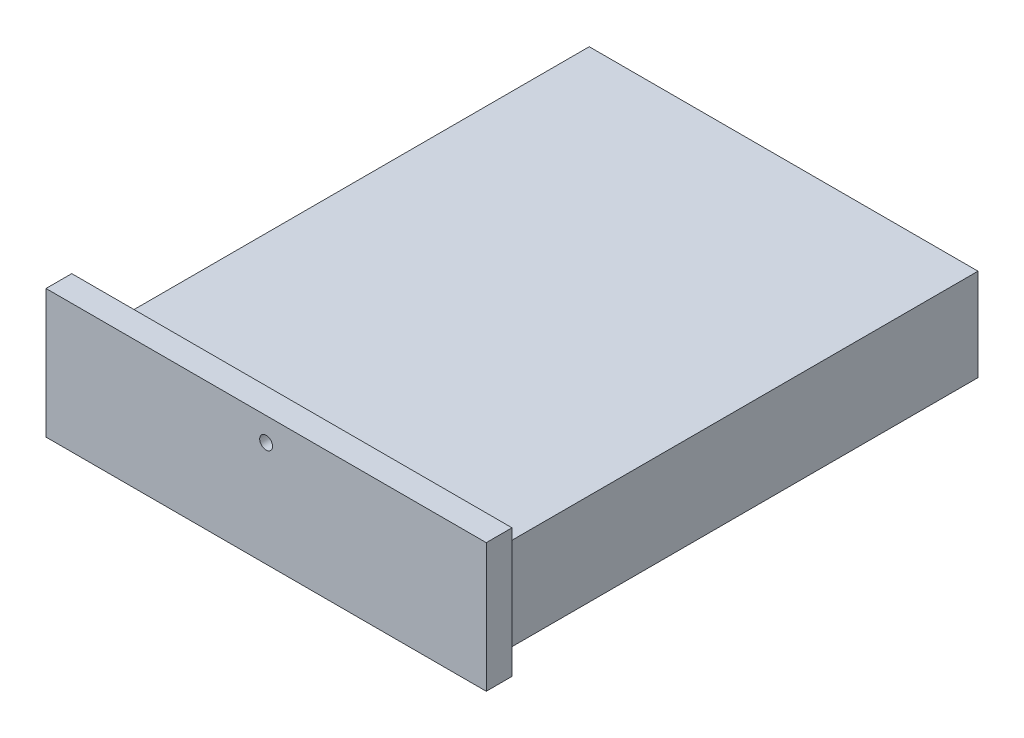
SolidWorks part; units mm, degrees
ref_plane "Front Plane" through (0, 0, 0) normal (0, 0, 1) x (1, 0, 0)
ref_plane "Top Plane" through (0, 0, 0) normal (0, 1, 0) x (1, 0, 0)
ref_plane "Right Plane" through (0, 0, 0) normal (1, 0, 0) x (0, 0, -1)
sketch "Sketch1" plane through (0, -22.3524, -0.0002) normal (0, 1, 0) x (1, 0, 0)
  line L4 (131.4337, 6.867) -> (131.3805, 6.867)
  line L5 (131.4337, 6.867) -> (131.3805, 6.867)
  line L6 (80.0805, 6.867) -> (80.0805, 25.967)
  line L7 (80.0805, 6.867) -> (80.0805, 25.967)
  line L14 (80.0805, 25.967) -> (64.9805, 25.967)
  line L15 (80.0805, 25.967) -> (64.9805, 25.967)
  line L16 (64.9805, 25.967) -> (64.9805, 5.967)
  line L17 (64.9805, 25.967) -> (64.9805, 5.967)
  line L26 (148.4829, 25.967) -> (133.3805, 25.967)
  line L27 (148.4829, 25.967) -> (133.3805, 25.967)
  line L28 (133.3805, 25.967) -> (133.3805, 5.967)
  line L29 (133.3805, 25.967) -> (133.3805, 5.967)
  line L75 (116.2805, 6.867) -> (114.2805, 6.867)
  line L76 (116.2805, 6.867) -> (114.2805, 6.867)
  line L77 (131.3805, 6.867) -> (131.3805, 25.967)
  line L78 (131.3805, 6.867) -> (131.3805, 25.967)
  line L79 (64.9805, 5.967) -> (62.5853, 5.967)
  line L80 (64.9805, 5.967) -> (62.5853, 5.967)
  line L81 (148.4829, 5.967) -> (148.4829, 25.967)
  line L82 (148.4829, 5.967) -> (148.4829, 25.967)
  line L83 (131.3805, 25.967) -> (116.2805, 25.967)
  line L84 (131.3805, 25.967) -> (116.2805, 25.967)
  line L85 (116.2805, 25.967) -> (116.2805, 6.867)
  line L86 (116.2805, 25.967) -> (116.2805, 6.867)
  line L87 (99.1805, 6.867) -> (97.1805, 6.867)
  line L88 (99.1805, 6.867) -> (97.1805, 6.867)
  line L89 (114.2805, 6.867) -> (114.2805, 25.967)
  line L90 (114.2805, 6.867) -> (114.2805, 25.967)
  line L91 (114.2805, 25.967) -> (99.1805, 25.967)
  line L92 (114.2805, 25.967) -> (99.1805, 25.967)
  line L93 (99.1805, 25.967) -> (99.1805, 6.867)
  line L94 (99.1805, 25.967) -> (99.1805, 6.867)
  line L95 (82.0805, 6.867) -> (80.0805, 6.867)
  line L96 (82.0805, 6.867) -> (80.0805, 6.867)
  line L97 (97.1805, 6.867) -> (97.1805, 25.967)
  line L98 (97.1805, 6.867) -> (97.1805, 25.967)
  line L99 (97.1805, 25.967) -> (82.0805, 25.967)
  line L100 (97.1805, 25.967) -> (82.0805, 25.967)
  line L101 (82.0805, 25.967) -> (82.0805, 6.867)
  line L102 (82.0805, 25.967) -> (82.0805, 6.867)
  line L111 (151.0746, 5.967) -> (148.4829, 5.967)
  line L112 (151.0746, 5.967) -> (148.4829, 5.967)
  line L149 (133.3805, 5.967) -> (131.4337, 5.967)
  line L150 (133.3805, 5.967) -> (131.4337, 5.967)
  line L151 (131.4337, 5.967) -> (131.4337, 6.867)
  line L152 (131.4337, 5.967) -> (131.4337, 6.867)
  arc A1 (62.5853, 5.967) -> (62.6384, 5.8755) centre (75.6644, 13.4963) ccw
  arc A2 (62.5853, 5.967) -> (62.6384, 5.8755) centre (75.6644, 13.4963) ccw
  spline S3 degree 3 poles (1819.909, 957.7332) (-1810.6582, -801.3047) (1974.7802, 742.3316) (-1777.865, -774.0547) knots -29.662381 -29.662381 -29.662381 -29.662381 32.998383 32.998383 32.998383 32.998383 only from (63.2069, 4.9792) to (64.6069, 3.1717)
  spline S4 degree 3 poles (550.872, -1936.6274) (70.2146, 117.013) (43.7863, 23.6148) (66.0259, 1.6806) (66.407, 1.3399) (67.5936, 0.3721) (68.44, -0.2041) (70.2044, -1.2669) (71.1081, -1.7488) (72.9497, -2.6116) (73.8899, -2.9905) (75.8005, -3.6662) (76.7705, -3.9643) (78.7232, -4.5262) (79.7054, -4.7912) (81.678, -5.2989) (82.6694, -5.5379) (84.658, -5.9748) (85.6562, -6.1718) (87.6567, -6.5442) (88.6588, -6.7199) (90.6645, -7.064) (91.6682, -7.2318) (94.6817, -7.721) (96.6958, -8.0266) (99.7213, -8.4164) (100.7307, -8.5334) (102.7546, -8.704) (103.7688, -8.7591) (105.8015, -8.8138) (106.8197, -8.8174) (108.859, -8.7878) (109.8772, -8.7557) (111.9061, -8.6254) (112.9167, -8.524) (114.9339, -8.2838) (115.9406, -8.1453) (118.9579, -7.7054) (120.9662, -7.374) (123.9704, -6.8548) (124.9707, -6.6779) (126.9684, -6.3136) (127.9654, -6.125) (129.9492, -5.7108) (130.9357, -5.4844) (132.8984, -4.9951) (133.8758, -4.7363) (135.824, -4.195) (136.7954, -3.9144) (138.7201, -3.289) (139.6729, -2.9424) (141.0799, -2.3428) (141.5456, -2.1311) (142.472, -1.69) (142.9335, -1.463) (143.8467, -0.9745) (144.3011, -0.7093) (145.165, -0.13) (145.5785, 0.1817) (146.1902, 0.6595) (146.3927, 0.8204) (146.7979, 1.1421) (147.0003, 1.3032) (165.0001, 15.9598) (168.1308, 48.001) (-1081.6017, 1578.8292) knots -0.820445 -0.820445 -0.820445 -0.820445 0.115071 0.115071 0.130696 0.130696 0.161946 0.161946 0.193196 0.193196 0.224446 0.224446 0.255696 0.255696 0.286946 0.286946 0.318196 0.318196 0.349446 0.349446 0.380696 0.380696 0.411946 0.411946 0.474446 0.474446 0.505696 0.505696 0.536946 0.536946 0.568196 0.568196 0.599446 0.599446 0.630696 0.630696 0.661946 0.661946 0.724446 0.724446 0.755696 0.755696 0.786946 0.786946 0.818196 0.818196 0.849446 0.849446 0.880696 0.880696 0.911946 0.911946 0.927571 0.927571 0.943196 0.943196 0.958821 0.958821 0.974446 0.974446 0.982259 0.982259 0.990071 0.990071 1.683487 1.683487 1.683487 1.683487 only from (64.6069, 3.1717) to (147.9528, 2.1042)
  spline S6 degree 3 poles (63.2069, 4.9792) (63.6398, 4.3447) (64.1129, 3.7449) (64.6069, 3.1717) knots 0 0 0 0 0.685452 0.685452 0.685452 0.685452 construction
  spline S7 degree 3 poles (64.6069, 3.1717) (64.9434, 2.7816) (65.2953, 2.4012) (66.0259, 1.6806) (66.407, 1.3399) (67.5936, 0.3721) (68.44, -0.2041) (70.2044, -1.2669) (71.1081, -1.7488) (72.9497, -2.6116) (73.8899, -2.9905) (75.8005, -3.6662) (76.7705, -3.9643) (78.7232, -4.5262) (79.7054, -4.7912) (81.678, -5.2989) (82.6694, -5.5379) (84.658, -5.9748) (85.6562, -6.1718) (87.6567, -6.5442) (88.6588, -6.7199) (90.6645, -7.064) (91.6682, -7.2318) (94.6817, -7.721) (96.6958, -8.0266) (99.7213, -8.4164) (100.7307, -8.5334) (102.7546, -8.704) (103.7688, -8.7591) (105.8015, -8.8138) (106.8197, -8.8174) (108.859, -8.7878) (109.8772, -8.7557) (111.9061, -8.6254) (112.9167, -8.524) (114.9339, -8.2838) (115.9406, -8.1453) (118.9579, -7.7054) (120.9662, -7.374) (123.9704, -6.8548) (124.9707, -6.6779) (126.9684, -6.3136) (127.9654, -6.125) (129.9492, -5.7108) (130.9357, -5.4844) (132.8984, -4.9951) (133.8758, -4.7363) (135.824, -4.195) (136.7954, -3.9144) (138.7201, -3.289) (139.6729, -2.9424) (141.0799, -2.3428) (141.5456, -2.1311) (142.472, -1.69) (142.9335, -1.463) (143.8467, -0.9745) (144.3011, -0.7093) (145.165, -0.13) (145.5785, 0.1817) (146.1902, 0.6595) (146.3927, 0.8204) (146.7979, 1.1421) (147.0003, 1.3032) (147.4557, 1.674) (147.7076, 1.8851) (147.9528, 2.1042) knots 0.099446 0.099446 0.099446 0.099446 0.115071 0.115071 0.130696 0.130696 0.161946 0.161946 0.193196 0.193196 0.224446 0.224446 0.255696 0.255696 0.286946 0.286946 0.318196 0.318196 0.349446 0.349446 0.380696 0.380696 0.411946 0.411946 0.474446 0.474446 0.505696 0.505696 0.536946 0.536946 0.568196 0.568196 0.599446 0.599446 0.630696 0.630696 0.661946 0.661946 0.724446 0.724446 0.755696 0.755696 0.786946 0.786946 0.818196 0.818196 0.849446 0.849446 0.880696 0.880696 0.911946 0.911946 0.927571 0.927571 0.943196 0.943196 0.958821 0.958821 0.974446 0.974446 0.982259 0.982259 0.990071 0.990071 1 1 1 1 construction
  spline S16 degree 3 poles (1374.7021, -1576.8824) (67.2274, 24.6762) (131.0951, -14.2876) (148.7396, 2.8512) (149.0893, 3.2405) (149.7556, 4.0536) (150.0701, 4.4713) (167.5144, 29.1367) (131.9775, 85.0745) (-1515.2945, 1110.8152) knots -0.67008 -0.67008 -0.67008 -0.67008 0.055384 0.055384 0.071009 0.071009 0.086634 0.086634 0.976126 0.976126 0.976126 0.976126 only from (147.9528, 2.1042) to (151.0746, 5.967)
  spline S17 degree 3 poles (147.9528, 2.1042) (148.0935, 2.2299) (148.232, 2.3582) (148.7396, 2.8512) (149.0893, 3.2405) (149.7556, 4.0536) (150.0701, 4.4713) (150.6182, 5.2462) (150.8542, 5.602) (151.0746, 5.967) knots 0.049688 0.049688 0.049688 0.049688 0.055384 0.055384 0.071009 0.071009 0.086634 0.086634 0.099446 0.099446 0.099446 0.099446
  spline S46 degree 3 poles (1819.9574, 957.7567) (-1810.8625, -801.4011) (1975.1528, 742.4834) (-1778.3942, -774.2686) knots -28.662659 -28.662659 -28.662659 -28.662659 34.001328 34.001328 34.001328 34.001328 only from (62.6384, 5.8755) to (63.2069, 4.9792)
  spline S47 degree 3 poles (62.6384, 5.8755) (62.8181, 5.5689) (63.0083, 5.2704) (63.2069, 4.9792) knots 0.685452 0.685452 0.685452 0.685452 1 1 1 1
  dimension "D1" = 0
sketch "Sketch3" plane through (0, 0.0002, -25.967) normal (0, 0, 1) x (1, 0, 0)
  line L1 (99.1806, 49.3018) -> (114.2806, 49.3018)
  line L2 (99.1806, 49.3018) -> (99.1806, 45.7197)
  line L3 (99.1806, 45.7197) -> (114.2806, 45.7197)
  line L4 (114.2806, 49.3018) -> (114.2806, 45.7197)
  line L6 (99.1806, 145.4576) -> (99.1805, -22.3524) construction
  line L7 (114.2806, 145.4575) -> (114.2805, -22.3525) construction
  dimension "D1" = 15.1
extrude "Boss-Extrude1" add sketch "Sketch3" along normal up to surface (19.1 mm away)
sketch "Sketch4" plane through (0, 0.0001, -6.867) normal (0, 0, 1) x (1, 0, 0)
  line L0 (97.1805, -22.3524) -> (97.1806, 145.4576) construction
  line L1 (98.1806, 50.7197) -> (115.2806, 50.7197)
  line L2 (98.1806, 50.7197) -> (98.1806, 45.7197)
  line L3 (98.1806, 45.7197) -> (115.2806, 45.7197)
  line L4 (115.2806, 50.7197) -> (115.2806, 45.7197)
  line L5 (99.1805, -22.3524) -> (99.1806, 145.4576) construction
  line L6 (97.1806, 37.2586) -> (99.1806, 37.2586) construction
  line L9 (98.1806, 37.2586) -> (98.1806, 50.3435) construction
  line L10 (114.2806, 37.2586) -> (116.2806, 37.2586) construction
  line L13 (115.2806, 37.2586) -> (115.2806, 50.5667) construction
  line L14 (114.2805, -22.3525) -> (114.2806, 145.4575) construction
  line L15 (116.2805, -22.3525) -> (116.2806, 145.4575) construction
  line L16 (114.2806, 45.7197) -> (99.1806, 45.7197) construction
  dimension "D1" = 5
extrude "Boss-Extrude2" add sketch "Sketch4" along normal blind 1
sketch "Sketch6" plane through (0, 0, -5.867) normal (0, 0, 1) x (1, 0, 0)
  line L0 (98.1806, 48.2197) -> (115.2806, 48.2197) construction
  line L1 (98.1806, 50.7197) -> (98.1806, 45.7197) construction
  line L2 (115.2806, 45.7197) -> (115.2806, 50.7197) construction
  line L3 (106.7306, 50.7197) -> (106.7306, 45.7197) construction
  line L4 (115.2806, 50.7197) -> (98.1806, 50.7197) construction
  line L5 (98.1806, 45.7197) -> (115.2806, 45.7197) construction
  point P0 (106.7306, 49.8079)
hole_wizard "Ø1.0mm Dowel Hole1" positions "Sketch7" profile "Sketch8" hole size "Ø1.0" standard "AS" end condition up to next
sketch "Sketch7" plane through (0, 0, -5.867) normal (0, 0, 1) x (1, 0, 0)
  point P0 (106.7306, 49.8079)
sketch "Sketch8" plane through (106.7306, 49.8079, -5.8666) normal (1, 0, 0) x (0, -1, 0)
  line L0 (0, 0) -> (0, 1)
  line L1 (0, 1) -> (0.25, 1)
  line L2 (0.25, 1) -> (0.25, 0)
  line L5 (0.25, 0) -> (0, 0)
  line L11 (0, -6.35) -> (0, 107.95) construction
  dimension "Thru Hole Dia." = 0.5
  dimension "Thru Hole Depth" = 1
